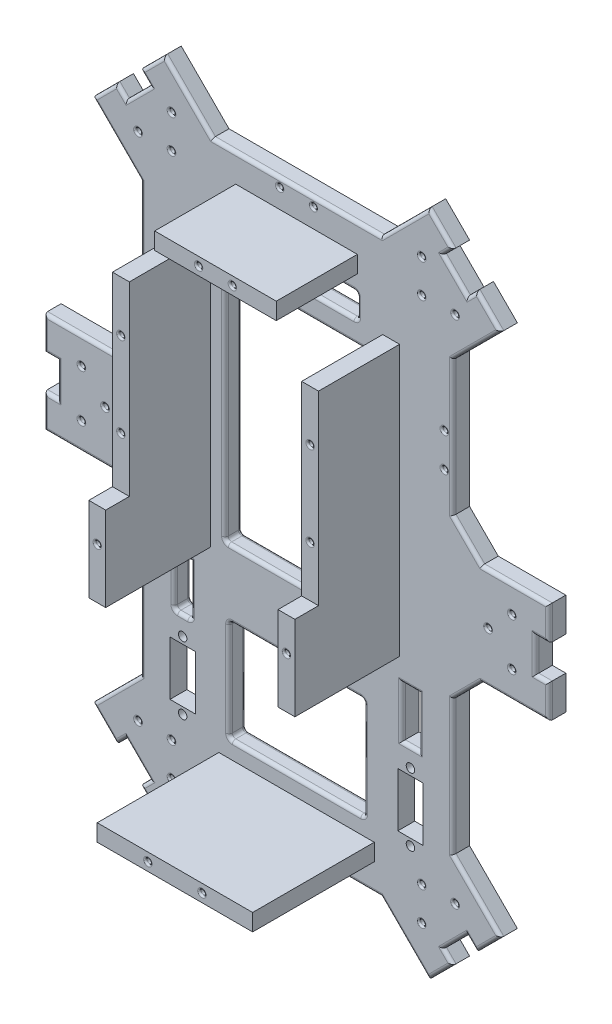
SolidWorks part; units mm, degrees
ref_plane "Płaszczyzna przednia" through (0, 0, 0) normal (0, 0, 1) x (1, 0, 0)
ref_plane "Płaszczyzna górna" through (0, 0, 0) normal (0, 1, 0) x (1, 0, 0)
ref_plane "Płaszczyzna prawa" through (0, 0, 0) normal (1, 0, 0) x (0, 0, -1)
sketch "Szkic1" plane through (0, 0, 0) normal (0, 0, 1) x (1, 0, 0)
  line L0 (0, 0) -> (-50, 0)
  line L1 (-50, 0) -> (-64.1421, 14.1421)
  line L2 (-64.1421, 14.1421) -> (-71.2132, 7.0711)
  line L3 (-71.2132, 7.0711) -> (-68.3848, 4.2426)
  line L4 (-68.3848, 4.2426) -> (-75.4558, -2.8284)
  line L5 (-75.4558, -2.8284) -> (-78.2843, 0)
  line L6 (-78.2843, 0) -> (-85.3553, -7.0711)
  line L7 (-85.3553, -7.0711) -> (-71.2132, -21.2132)
  line L8 (-71.2132, -21.2132) -> (-71.2132, -61.2132)
  line L9 (0, 0) -> (14.1421, 14.1421)
  line L10 (14.1421, 14.1421) -> (21.2132, 7.0711)
  line L11 (21.2132, 7.0711) -> (18.3848, 4.2426)
  line L12 (18.3848, 4.2426) -> (25.4558, -2.8284)
  line L13 (25.4558, -2.8284) -> (28.2843, 0)
  line L14 (28.2843, 0) -> (35.3553, -7.0711)
  line L15 (35.3553, -7.0711) -> (21.2132, -21.2132)
  line L16 (21.2132, -21.2132) -> (21.2132, -61.2132)
  line L17 (-71.2132, -61.2132) -> (-79.6985, -69.6985)
  line L18 (-79.6985, -69.6985) -> (-99.6985, -69.6985)
  line L19 (-99.6985, -69.6985) -> (-99.6985, -79.6985)
  line L20 (-99.6985, -79.6985) -> (-95.6985, -79.6985)
  line L21 (-95.6985, -79.6985) -> (-95.6985, -89.6985)
  line L22 (-95.6985, -89.6985) -> (-99.6985, -89.6985)
  line L23 (-99.6985, -89.6985) -> (-99.6985, -99.6985)
  line L24 (-99.6985, -99.6985) -> (-79.6985, -99.6985)
  line L25 (21.2132, -61.2132) -> (29.6985, -69.6985)
  line L26 (29.6985, -69.6985) -> (49.6985, -69.6985)
  line L27 (49.6985, -69.6985) -> (49.6985, -79.6985)
  line L28 (49.6985, -79.6985) -> (45.6985, -79.6985)
  line L29 (45.6985, -79.6985) -> (45.6985, -89.6985)
  line L30 (45.6985, -89.6985) -> (49.6985, -89.6985)
  line L31 (49.6985, -89.6985) -> (49.6985, -99.6985)
  line L32 (49.6985, -99.6985) -> (29.6985, -99.6985)
  line L33 (29.6985, -99.6985) -> (21.2132, -108.1838)
  line L34 (-79.6985, -99.6985) -> (-71.2132, -108.1838)
  line L35 (-71.2132, -108.1838) -> (-71.2132, -148.1838)
  line L36 (21.2132, -108.1838) -> (21.2132, -148.1838)
  line L37 (-71.2132, -148.1838) -> (-85.3553, -162.3259)
  line L38 (-85.3553, -162.3259) -> (-78.2843, -169.397)
  line L39 (-78.2843, -169.397) -> (-75.4558, -166.5685)
  line L40 (-75.4558, -166.5685) -> (-68.3848, -173.6396)
  line L41 (-68.3848, -173.6396) -> (-71.2132, -176.468)
  line L42 (-71.2132, -176.468) -> (-64.1421, -183.5391)
  line L43 (-64.1421, -183.5391) -> (-50, -169.397)
  line L44 (21.2132, -148.1838) -> (35.3553, -162.3259)
  line L45 (35.3553, -162.3259) -> (28.2843, -169.397)
  line L46 (28.2843, -169.397) -> (25.4558, -166.5685)
  line L47 (25.4558, -166.5685) -> (18.3848, -173.6396)
  line L48 (18.3848, -173.6396) -> (21.2132, -176.468)
  line L49 (21.2132, -176.468) -> (14.1421, -183.5391)
  line L50 (14.1421, -183.5391) -> (0, -169.397)
  line L51 (-50, -169.397) -> (0, -169.397)
  dimension "D1" = 225
  dimension "D2" = 225
  dimension "D3" = 20
  dimension "D4" = 20
  dimension "D5" = 10
  dimension "D6" = 4
  dimension "D7" = 50
  dimension "D8" = 10
  dimension "D9" = 10
  dimension "D10" = 20
  dimension "D11" = 4
  dimension "D12" = 10
  dimension "D13" = 4
  dimension "D14" = 10
  dimension "D15" = 4
  dimension "D16" = 10
  dimension "D17" = 20
  dimension "D18" = 225
  dimension "D19" = 40
  dimension "D20" = 12
  dimension "D21" = 20
  dimension "D22" = 10
  dimension "D23" = 4
  dimension "D24" = 10
  dimension "D25" = 4
  dimension "D26" = 10
  dimension "D27" = 20
  dimension "D29" = 12
  dimension "D30" = 20
  dimension "D31" = 10
  dimension "D32" = 4
  dimension "D33" = 10
  dimension "D34" = 4
  dimension "D35" = 10
  dimension "D36" = 20
  dimension "D37" = 12
  dimension "D38" = 12
  dimension "D39" = 40
  dimension "D40" = 40
  dimension "D41" = 20
  dimension "D42" = 10
  dimension "D43" = 4
  dimension "D44" = 10
  dimension "D45" = 4
  dimension "D46" = 10
  dimension "D47" = 20
  dimension "D48" = 20
  dimension "D49" = 10
  dimension "D50" = 4
  dimension "D51" = 10
  dimension "D52" = 4
  dimension "D53" = 10
  dimension "D54" = 20
  dimension "D55" = 135
  dimension "D56" = 90
  dimension "D57" = 270
  dimension "D58" = 225
  dimension "D59" = 225
  dimension "D60" = 135
extrude "Dodanie-wyciągnięcie1" add sketch "Szkic1" along normal blind 5 contours L36 L44 L45 L46 L47 L48 L49 L50 L51 L43 L42 L41 L40 L39 L38 L37 L35 L34 L24 L23 L22 L21 L20 L19 L18 L17 L8 L7 L6 L5 L4 L3 L2 L1 L0 L9 L10 L11 L12 L13 L14 L15 L16 L25 L26 L27 L28 L29 L30 L31 L32 L33
sketch "Szkic11" plane through (0, 0, 5) normal (0, 0, 1) x (1, 0, 0)
  line L0 (-79.6985, -69.6985) -> (-99.6985, -69.6985) construction
  line L1 (-85.3553, -7.0711) -> (-71.2132, -21.2132) construction
  line L2 (-99.6985, -69.6985) -> (-99.6985, -79.6985) construction
  line L3 (-99.6985, -99.6985) -> (-79.6985, -99.6985) construction
  line L4 (-78.2843, 0) -> (-85.3553, -7.0711) construction
  line L5 (-50, 0) -> (-64.1421, 14.1421) construction
  line L6 (-64.1421, 14.1421) -> (-71.2132, 7.0711) construction
  line L7 (14.1421, 14.1421) -> (21.2132, 7.0711) construction
  line L8 (35.3553, -7.0711) -> (21.2132, -21.2132) construction
  line L9 (28.2843, 0) -> (35.3553, -7.0711) construction
  line L10 (0, 0) -> (14.1421, 14.1421) construction
  line L11 (49.6985, -89.6985) -> (49.6985, -99.6985) construction
  line L12 (49.6985, -99.6985) -> (29.6985, -99.6985) construction
  line L13 (49.6985, -69.6985) -> (49.6985, -79.6985) construction
  line L14 (29.6985, -69.6985) -> (49.6985, -69.6985) construction
  line L15 (21.2132, -176.468) -> (14.1421, -183.5391) construction
  line L16 (14.1421, -183.5391) -> (0, -169.397) construction
  line L17 (35.3553, -162.3259) -> (28.2843, -169.397) construction
  line L18 (21.2132, -148.1838) -> (35.3553, -162.3259) construction
  line L19 (-85.3553, -162.3259) -> (-78.2843, -169.397) construction
  line L20 (-71.2132, -176.468) -> (-64.1421, -183.5391) construction
  line L21 (-64.1421, -183.5391) -> (-50, -169.397) construction
  line L22 (-71.2132, -148.1838) -> (-85.3553, -162.3259) construction
  line L23 (-99.6985, -89.6985) -> (-99.6985, -99.6985) construction
  circle A0 centre (-81.6985, -84.6985) radius 0.8
  circle A1 centre (-88.6985, -77.6985) radius 0.8
  circle A2 centre (-88.6985, -91.6985) radius 0.8
  circle A3 centre (-62.0208, -9.1924) radius 0.8
  circle A4 centre (-62.0208, 0.7071) radius 0.8
  circle A5 centre (-71.9203, -9.1924) radius 0.8
  circle A6 centre (12.0208, -9.1924) radius 0.8
  circle A7 centre (12.0208, 0.7071) radius 0.8
  circle A8 centre (21.9203, -9.1924) radius 0.8
  circle A9 centre (31.6985, -84.6985) radius 0.8
  circle A10 centre (38.6985, -77.6985) radius 0.8
  circle A11 centre (38.6985, -91.6985) radius 0.8
  circle A12 centre (12.0208, -160.2046) radius 0.8
  circle A13 centre (21.9203, -160.2046) radius 0.8
  circle A14 centre (12.0208, -170.1041) radius 0.8
  circle A15 centre (-62.0208, -160.2046) radius 0.8
  circle A16 centre (-71.9203, -160.2046) radius 0.8
  circle A17 centre (-62.0208, -170.1041) radius 0.8
  dimension "D1" = 1.6
  dimension "D4" = 1.6
  dimension "D5" = 1.6
  dimension "D10" = 1.6
  dimension "D11" = 1.6
  dimension "D12" = 1.6
  dimension "D19" = 1.6
  dimension "D20" = 1.6
  dimension "D21" = 1.6
  dimension "D30" = 1.6
  dimension "D31" = 1.6
  dimension "D32" = 1.6
  dimension "D41" = 1.6
  dimension "D42" = 1.6
  dimension "D43" = 1.6
  dimension "D50" = 1.6
  dimension "D51" = 1.6
  dimension "D52" = 1.6
  dimension "D2" = 15
  dimension "D3" = 18
  dimension "D6" = 7
  dimension "D7" = 7
  dimension "D8" = 8
  dimension "D9" = 8
  dimension "D13" = 18
  dimension "D14" = 15
  dimension "D15" = 8
  dimension "D16" = 8
  dimension "D17" = 11
  dimension "D18" = 11
  dimension "D22" = 18
  dimension "D23" = 15
  dimension "D24" = 11
  dimension "D25" = 11
  dimension "D26" = 8
  dimension "D27" = 8
  dimension "D28" = 14
  dimension "D29" = 14
  dimension "D33" = 18
  dimension "D34" = 15
  dimension "D35" = 11
  dimension "D36" = 11
  dimension "D37" = 8
  dimension "D38" = 8
  dimension "D39" = 14
  dimension "D40" = 7
  dimension "D44" = 18
  dimension "D45" = 15
  dimension "D46" = 11
  dimension "D47" = 11
  dimension "D48" = 8
  dimension "D49" = 8
  dimension "D53" = 18
  dimension "D54" = 11
  dimension "D55" = 11
  dimension "D56" = 8
  dimension "D57" = 15
  dimension "D58" = 8
  dimension "D59" = 14
  dimension "D60" = 14
  dimension "D61" = 14
  dimension "D62" = 11
  dimension "D63" = 11
extrude "Wytnij-wyciągnięcie7" cut sketch "Szkic11" against normal blind 60 and the other way blind 42
sketch "Szkic12" plane through (0, 0, 5) normal (0, 0, 1) x (1, 0, 0)
  line L0 (0, 0) -> (-50, 0) construction
  line L1 (-71.2132, -21.2132) -> (-71.2132, -61.2132) construction
  line L2 (-50, -169.397) -> (0, -169.397) construction
  line L3 (21.2132, -21.2132) -> (21.2132, -61.2132) construction
  circle A0 centre (-30, -2.5) radius 0.75
  circle A1 centre (-20, -2.5) radius 0.75
  circle A2 centre (-30, -166.897) radius 0.75
  circle A3 centre (-20, -166.897) radius 0.75
  circle A4 centre (-68.7132, -40.5) radius 0.75
  circle A5 centre (-68.7132, -50.5) radius 0.75
  circle A6 centre (18.7132, -40.5) radius 0.75
  circle A7 centre (18.7132, -50.5) radius 0.75
  dimension "D2" = 1.5
  dimension "D3" = 1.5
  dimension "D8" = 1.5
  dimension "D9" = 1.5
  dimension "D15" = 1.5
  dimension "D16" = 1.5
  dimension "D17" = 1.5
  dimension "D18" = 1.5
  dimension "D1" = 2.5
  dimension "D4" = 2.5
  dimension "D5" = 20
  dimension "D6" = 10
  dimension "D7" = 20
  dimension "D10" = 2.5
  dimension "D11" = 2.5
  dimension "D12" = 20
  dimension "D13" = 10
  dimension "D14" = 20
  dimension "D19" = 2.5
  dimension "D20" = 2.5
  dimension "D21" = 2.5
  dimension "D22" = 2.5
  dimension "D23" = 40.5
  dimension "D24" = 50.5
  dimension "D25" = 40.5
  dimension "D26" = 50.5
extrude "Wytnij-wyciągnięcie8" cut sketch "Szkic12" against normal blind 66 and the other way blind 36
sketch "Szkic13" plane through (0, 0, 0) normal (0, 0, 1) x (1, 0, 0)
  line L0 (0, 0) -> (-50, 0) construction
  line L1 (-46.2132, -31.5) -> (-3.7868, -31.5)
  line L2 (-46.2132, -31.5) -> (-46.2132, -101.5)
  line L3 (-46.2132, -101.5) -> (-3.7868, -101.5)
  line L4 (-3.7868, -31.5) -> (-3.7868, -101.5)
  line L9 (-71.2132, -21.2132) -> (-71.2132, -61.2132) construction
  line L10 (21.2132, -21.2132) -> (21.2132, -61.2132) construction
  line L11 (-71.2132, -108.1838) -> (-71.2132, -148.1838) construction
  line L12 (-45.0032, -121.397) -> (-5.0032, -121.397)
  line L13 (-45.0032, -121.397) -> (-45.0032, -151.397)
  line L14 (-45.0032, -151.397) -> (-5.0032, -151.397)
  line L15 (-5.0032, -121.397) -> (-5.0032, -151.397)
  line L16 (21.2132, -108.1838) -> (21.2132, -148.1838) construction
  line L17 (-50, -169.397) -> (0, -169.397) construction
  line L19 (-61.2132, -111.5) -> (-56.2132, -111.5)
  line L20 (-61.2132, -111.5) -> (-61.2132, -126.5)
  line L21 (-61.2132, -126.5) -> (-56.2132, -126.5)
  line L22 (-56.2132, -111.5) -> (-56.2132, -126.5)
  line L23 (-62.4632, -134) -> (-54.9632, -134)
  line L24 (-62.4632, -134) -> (-62.4632, -150)
  line L25 (-62.4632, -150) -> (-54.9632, -150)
  line L26 (-54.9632, -134) -> (-54.9632, -150)
  line L31 (4.9632, -134) -> (12.4632, -134)
  line L32 (4.9632, -134) -> (4.9632, -150)
  line L33 (4.9632, -150) -> (12.4632, -150)
  line L34 (12.4632, -134) -> (12.4632, -150)
  line L35 (-43.0032, -18) -> (-7.0032, -18)
  line L36 (-43.0032, -18) -> (-43.0032, -25)
  line L37 (-43.0032, -25) -> (-7.0032, -25)
  line L38 (-7.0032, -18) -> (-7.0032, -25)
  line L39 (6.2132, -111.5) -> (11.2132, -111.5)
  line L40 (6.2132, -111.5) -> (6.2132, -126.5)
  line L41 (6.2132, -126.5) -> (11.2132, -126.5)
  line L42 (11.2132, -111.5) -> (11.2132, -126.5)
  circle A0 centre (8.7132, -132) radius 1.25
  circle A1 centre (8.7132, -152) radius 1.25
  circle A2 centre (-58.7132, -132) radius 1.25
  circle A3 centre (-58.7132, -152) radius 1.25
  dimension "D39" = 2.5
  dimension "D40" = 2.5
  dimension "D30" = 2.5
  dimension "D41" = 2.5
  dimension "D1" = 70
  dimension "D2" = 31.5
  dimension "D3" = 25
  dimension "D5" = 25
  dimension "D6" = 15
  dimension "D7" = 12.603
  dimension "D8" = 7.5
  dimension "D9" = 40
  dimension "D10" = 26.21
  dimension "D11" = 26.2164
  dimension "D12" = 30
  dimension "D13" = 18
  dimension "D14" = 2
  dimension "D15" = 10
  dimension "D16" = 5
  dimension "D17" = 10
  dimension "D18" = 15
  dimension "D19" = 8.75
  dimension "D20" = 7.5
  dimension "D21" = 7.5
  dimension "D22" = 16
  dimension "D23" = 0
  dimension "D24" = 7.5
  dimension "D25" = 5
  dimension "D26" = 3.75
  dimension "D27" = 3.75
  dimension "D28" = 8.75
  dimension "D29" = 16
  dimension "D31" = 9.9664
  dimension "D32" = 28.21
  dimension "D33" = 36
  dimension "D34" = 28.2164
  dimension "D35" = 7
  dimension "D36" = 18
  dimension "D37" = 3.75
  dimension "D38" = 3.75
  dimension "50" = 20
  dimension "D42" = 2
  dimension "D43" = 2
  dimension "D44" = 10
extrude "Wytnij-wyciągnięcie9" cut sketch "Szkic13" against normal blind 47 and the other way blind 54
sketch "Szkic14" plane through (0, 0, 5) normal (0, 0, 1) x (1, 0, 0)
  line L0 (-50.4982, -25) -> (-55.4982, -25)
  line L1 (-55.4982, -25) -> (-55.4982, -105)
  line L2 (-55.4982, -105) -> (-50.4982, -105)
  line L3 (-50.4982, -105) -> (-50.4982, -25)
  line L4 (5.5018, -25) -> (5.5018, -105)
  line L5 (5.5018, -105) -> (0.5018, -105)
  line L6 (0.5018, -25) -> (5.5018, -25)
  line L7 (0.5018, -105) -> (0.5018, -25)
  line L8 (-46.2132, -101.5) -> (-46.2132, -31.5) construction
  line L10 (-5.0032, -151.397) -> (-45.0032, -151.397) construction
  line L11 (0, 0) -> (-50, 0) construction
  line L12 (-3.7868, -31.5) -> (-3.7868, -101.5) construction
  line L13 (-48.0032, -156.397) -> (-2.0032, -156.397)
  line L14 (-2.0032, -156.397) -> (-2.0032, -161.397)
  line L15 (-2.0032, -161.397) -> (-48.0032, -161.397)
  line L16 (-48.0032, -161.397) -> (-48.0032, -156.397)
  line L18 (-71.2132, -108.1838) -> (-71.2132, -148.1838) construction
  line L19 (-43.0032, -13.197) -> (-7.0032, -13.197)
  line L20 (-7.0032, -13.197) -> (-7.0032, -8.197)
  line L21 (-7.0032, -8.197) -> (-43.0032, -8.197)
  line L22 (-43.0032, -8.197) -> (-43.0032, -13.197)
  line L24 (-71.2132, -21.2132) -> (-71.2132, -61.2132) construction
  circle A0 centre (-30.0032, -10.697) radius 0.75
  circle A1 centre (-20.0032, -10.697) radius 0.75
  circle A2 centre (-33.0032, -158.897) radius 0.75
  circle A3 centre (-17.0032, -158.897) radius 0.75
  circle A4 centre (-52.9982, -40) radius 0.75
  circle A5 centre (-52.9982, -65) radius 0.75
  circle A6 centre (-52.9982, -90) radius 0.75
  circle A7 centre (3.0018, -40) radius 0.75
  circle A8 centre (3.0018, -65) radius 0.75
  circle A9 centre (3.0018, -90) radius 0.75
  dimension "D21" = 1.5
  dimension "D22" = 1.5
  dimension "D26" = 1.5
  dimension "D27" = 1.5
  dimension "D33" = 1.5
  dimension "D34" = 1.5
  dimension "D35" = 1.5
  dimension "D42" = 1.5
  dimension "D43" = 1.5
  dimension "D44" = 1.5
  dimension "D1" = 80
  dimension "D2" = 5
  dimension "D3" = 5
  dimension "D4" = 80
  dimension "D5" = 51
  dimension "D6" = 4.285
  dimension "D7" = 4.2886
  dimension "D8" = 25
  dimension "D9" = 25
  dimension "D10" = 5
  dimension "D11" = 5
  dimension "D12" = 46
  dimension "D13" = 23.21
  dimension "D14" = 143.2
  dimension "D15" = 5
  dimension "D16" = 28.21
  dimension "D17" = 36
  dimension "D18" = 2.5
  dimension "D19" = 2.5
  dimension "D20" = 10
  dimension "D23" = 13
  dimension "D24" = 2.5
  dimension "D25" = 2.5
  dimension "D28" = 16
  dimension "D29" = 15
  dimension "D30" = 2.5
  dimension "D31" = 2.5
  dimension "D32" = 2.5
  dimension "D36" = 25
  dimension "D37" = 25
  dimension "D38" = 15
  dimension "D39" = 2.5
  dimension "D40" = 2.5
  dimension "D41" = 2.5
  dimension "D45" = 15
  dimension "D46" = 25
  dimension "D47" = 25
extrude "Dodanie-wyciągnięcie7" add sketch "Szkic14" along normal blind 24
extrude "Dodanie-wyciągnięcie8" add sketch "Szkic14<9>" along normal blind 36 contours L16 L15 L14 L13 A3 A2 region at (-25.0032, -158.897, 5)
sketch "Szkic14<9>" plane through (0, 0, 5) normal (0, 0, 1) x (1, 0, 0) same geometry as "Szkic14"
sketch "Szkic17" plane through (0, 0, 0) normal (0, 0, 1) x (1, 0, 0)
  line L0 (-50.4982, -80) -> (-55.4982, -80)
  line L1 (-50.4982, -105) -> (-50.4982, -25) construction
  line L2 (-55.4982, -25) -> (-55.4982, -105) construction
  line L3 (-55.4982, -80) -> (-55.4982, -105)
  line L4 (-55.4982, -105) -> (-50.4982, -105)
  line L5 (-50.4982, -105) -> (-50.4982, -80)
  line L6 (0.5018, -105) -> (5.5018, -105)
  line L7 (5.5018, -105) -> (5.5018, -80)
  line L8 (5.5018, -105) -> (5.5018, -25) construction
  line L9 (5.5018, -80) -> (0.5018, -80)
  line L10 (0.5018, -25) -> (0.5018, -105) construction
  line L11 (0.5018, -80) -> (0.5018, -105)
  circle A0 centre (-52.9982, -90) radius 0.75
  circle A1 centre (3.0018, -90) radius 0.75
  dimension "D3" = 1.5
  dimension "D4" = 1.5
  dimension "D1" = 25
  dimension "D2" = 25
extrude "Dodanie-wyciągnięcie9" add sketch "Szkic17" along normal blind 36
fillet "Zaokrąglenie3" radius 1 52 edges at (-97.6985, -79.6985, 5) (-95.6985, -84.6985, 5) (-97.6985, -89.6985, 5) (-99.6985, -94.6985, 5) (-89.6985, -99.6985, 5) (-75.4558, -103.9411, 5) (-71.2132, -128.1838, 5) (-78.2843, -155.2548, 5) (-76.8701, -167.9828, 5) (-69.799, -175.0538, 5) (-81.8198, -165.8614, 5) (-71.9203, -170.1041, 5) (-67.6777, -180.0036, 5) (-57.0711, -176.468, 5) (-25, -169.397, 5) (7.0711, -176.468, 5) (17.6777, -180.0036, 5) (19.799, -175.0538, 5) (21.9203, -170.1041, 5) (26.8701, -167.9828, 5) (31.8198, -165.8614, 5) (28.2843, -155.2548, 5) (21.2132, -128.1838, 5) (25.4558, -103.9411, 5) (39.6985, -99.6985, 5) (49.6985, -94.6985, 5) (47.6985, -89.6985, 5) (45.6985, -84.6985, 5) (47.6985, -79.6985, 5) (49.6985, -74.6985, 5) (39.6985, -69.6985, 5) (25.4558, -65.4558, 5) (21.2132, -41.2132, 5) (28.2843, -14.1421, 5) (31.8198, -3.5355, 5) (26.8701, -1.4142, 5) (21.9203, 0.7071, 5) (19.799, 5.6569, 5) (17.6777, 10.6066, 5) (7.0711, 7.0711, 5) (-25, 0, 5) (-69.799, 5.6569, 5) (-67.6777, 10.6066, 5) (-57.0711, 7.0711, 5) (-71.9203, 0.7071, 5) (-76.8701, -1.4142, 5) (-81.8198, -3.5355, 5) (-78.2843, -14.1421, 5) (-71.2132, -41.2132, 5) (-75.4558, -65.4558, 5) (-89.6985, -69.6985, 5) (-99.6985, -74.6985, 5)
fillet "Zaokrąglenie4" radius 1 50 edges at (-56.2132, -119, 5) (-61.2132, -119, 5) (-61.2132, -119, 0) (-56.2132, -119, 0) (-45.0032, -136.397, 5) (-5.0032, -136.397, 5) (-5.0032, -136.397, 0) (-45.0032, -136.397, 0) (-46.2132, -66.5, 5) (-3.7868, -66.5, 5) (-3.7868, -66.5, 0) (-46.2132, -66.5, 0) (-7.0032, -21.5, 5) (-43.0032, -21.5, 5) (-43.0032, -21.5, 0) (-7.0032, -21.5, 0) (-58.7132, -126.5, 5) (-61.2132, -126.5, 2.5) (-58.7132, -126.5, 0) (-56.2132, -126.5, 2.5) (-25.0032, -151.397, 5) (-45.0032, -151.397, 2.5) (-25.0032, -151.397, 0) (-5.0032, -151.397, 2.5) (-25.0032, -121.397, 5) (-5.0032, -121.397, 2.5) (-25.0032, -121.397, 0) (-45.0032, -121.397, 2.5) (-25, -101.5, 5) (-46.2132, -101.5, 2.5) (-25, -101.5, 0) (-3.7868, -101.5, 2.5) (-25, -31.5, 5) (-3.7868, -31.5, 2.5) (-25, -31.5, 0) (-46.2132, -31.5, 2.5) (-25.0032, -18, 5) (-7.0032, -18, 2.5) (-25.0032, -18, 0) (-43.0032, -18, 2.5) (-25.0032, -25, 5) (-43.0032, -25, 2.5) (-25.0032, -25, 0) (-7.0032, -25, 2.5) (-58.7132, -111.5, 0) (-58.7132, -111.5, 5) (8.7132, -126.5, 5) (11.2132, -119, 5) (8.7132, -111.5, 5) (6.2132, -119, 5)
fillet "Zaokrąglenie5" radius 0.5 36 edges at (12.8208, -170.1041, 5) (12.8208, -160.2046, 5) (22.7203, -160.2046, 5) (-19.25, -166.897, 5) (-29.25, -166.897, 5) (-61.2208, -170.1041, 5) (-61.2208, -160.2046, 5) (-71.1203, -160.2046, 5) (-67.9632, -50.5, 5) (-67.9632, -40.5, 5) (39.4985, -91.6985, 5) (32.4985, -84.6985, 5) (39.4985, -77.6985, 5) (19.4632, -50.5, 5) (19.4632, -40.5, 5) (22.7203, -9.1924, 5) (12.8208, -9.1924, 5) (-29.25, -2.5, 5) (-19.25, -2.5, 5) (12.8208, 0.7071, 5) (-61.2208, -9.1924, 5) (-71.1203, -9.1924, 5) (-61.2208, 0.7071, 5) (-87.8985, -91.6985, 5) (-80.8985, -84.6985, 5) (-87.8985, -77.6985, 5) (-19.2532, -10.697, 29) (-29.2532, -10.697, 29) (-32.2532, -158.897, 41) (-16.2532, -158.897, 41) (3.7518, -90, 36) (3.7518, -65, 29) (3.7518, -40, 29) (-52.2482, -90, 36) (-52.2482, -65, 29) (-52.2482, -40, 29)
